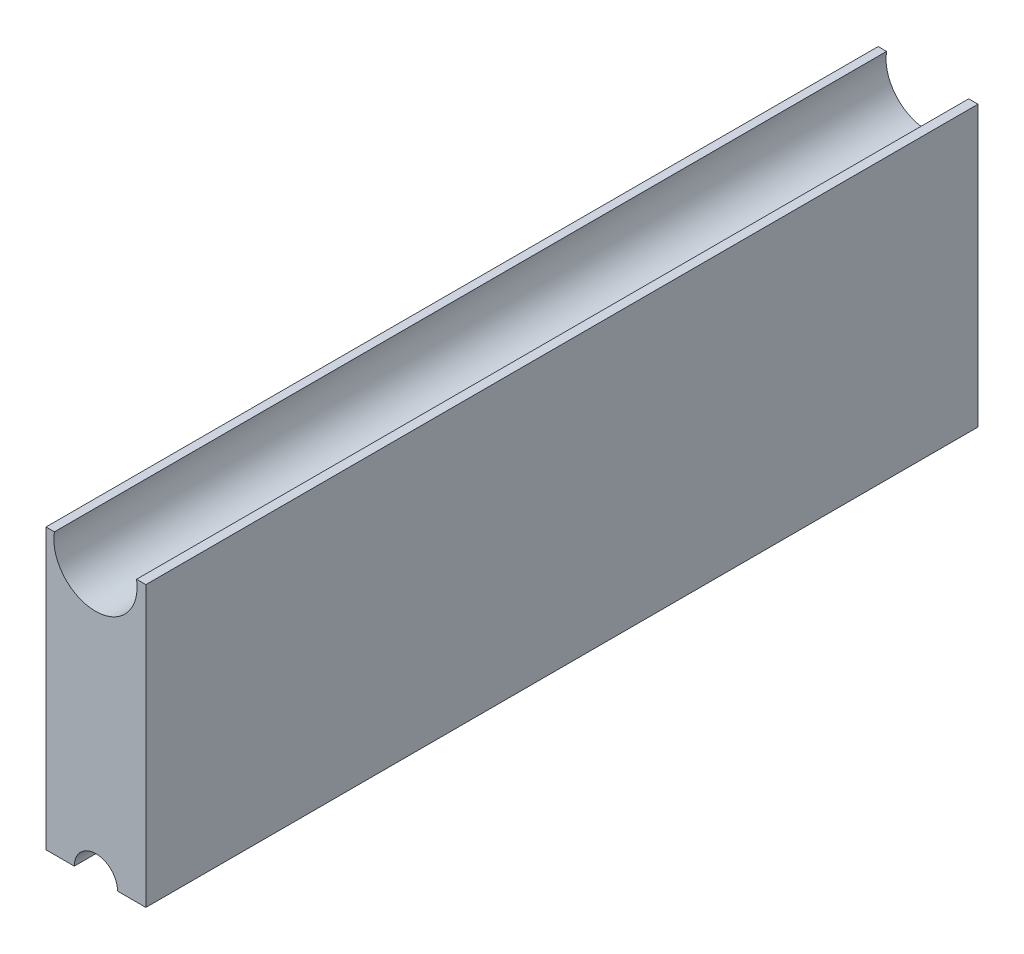
SolidWorks part; units mm, degrees
material "ABS"
ref_plane "Front Plane" through (0, 0, 0) normal (0, 0, 1) x (1, 0, 0)
ref_plane "Top Plane" through (0, 0, 0) normal (0, 1, 0) x (1, 0, 0)
ref_plane "Right Plane" through (0, 0, 0) normal (1, 0, 0) x (0, 0, -1)
sketch "Sketch1" plane through (0, 0, 0) normal (0, 0, 1) x (1, 0, 0)
  line L16 (-5.207, -4.826) -> (-12.827, -4.826)
  line L17 (-5.207, -4.826) -> (-5.207, -26.162)
  line L18 (-12.827, -4.826) -> (-12.827, -26.162)
  line L19 (-5.207, -26.162) -> (-12.827, -26.162)
  circle A0 centre (-9.051, -5.334) radius 3.175
  circle A1 centre (-9.017, -26.162) radius 1.651
  point P0 (-9.017, -26.162)
  dimension "D9" = 6.35
  dimension "D10" = 3.302
  dimension "D2" = 21.336
  dimension "D3" = 7.62
  dimension "D4" = 3.81
  dimension "D5" = 0
  dimension "D11" = 20.828
extrude "Boss-Extrude4" add sketch "Sketch1" along normal blind 63.5 contours A1 L19 L17 A0 L18 region at (-9.0123, -16.4298, 0)
